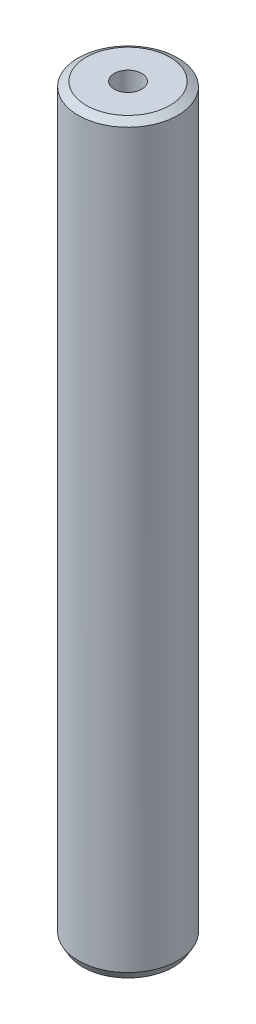
SolidWorks part; units mm, degrees
ref_plane "Front Plane" through (0, 0, 0) normal (0, 0, 1) x (1, 0, 0)
ref_plane "Top Plane" through (0, 0, 0) normal (0, 1, 0) x (1, 0, 0)
ref_plane "Right Plane" through (0, 0, 0) normal (1, 0, 0) x (0, 0, -1)
sketch "Sketch1" plane through (0, 0, 0) normal (0, 1, 0) x (1, 0, 0)
  circle A0 centre (0, 0) radius 17.5
  dimension "SHAFT_OD" = 35
extrude "Boss-Extrude1" add sketch "Sketch1" along normal blind 261.6072
sketch "Sketch2" plane through (0, 0, 0) normal (0, 1, 0) x (1, 0, 0)
  circle A0 centre (0, 0) radius 4.8209
  dimension "BORE_D" = 9.6417
extrude "Cut-Extrude1" cut sketch "Sketch2" along normal through all
chamfer "Chamfer1" distance 1.6215 angle 60 2 edges at (0, 261.6072, 17.5) (0, 0, 17.5) first distance on face at (0, 261.6072, 17.5) first distance on face at (0, 0, 4.8209)
